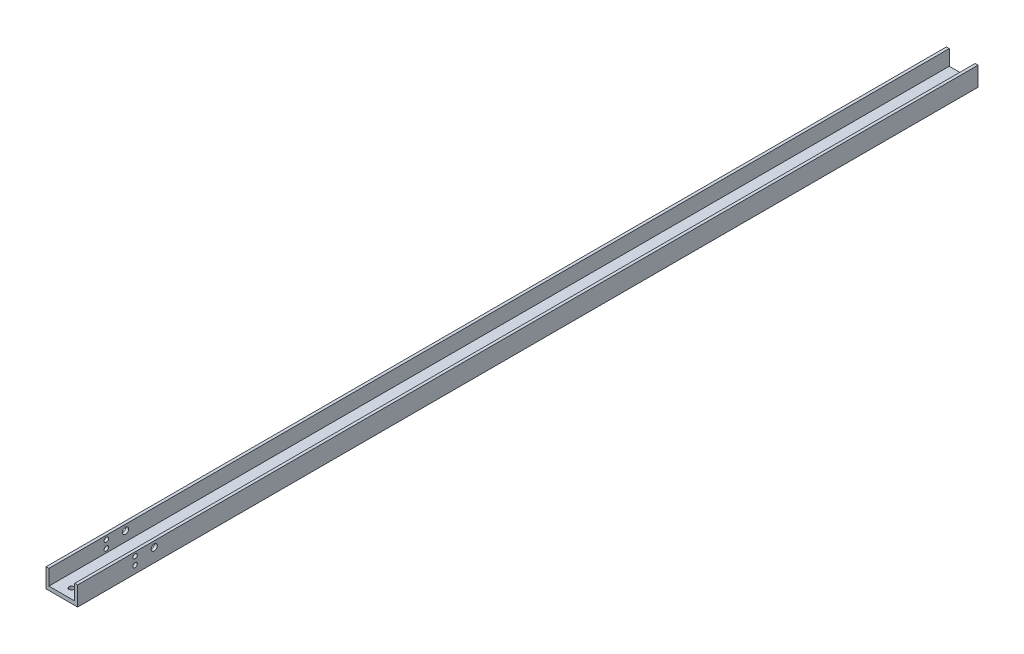
SolidWorks part; units mm, degrees
material "Alliage 1060"
ref_plane "Plan de face" through (0, 0, 0) normal (0, 0, 1) x (1, 0, 0)
ref_plane "Plan de dessus" through (0, 0, 0) normal (0, 1, 0) x (1, 0, 0)
ref_plane "Plan de droite" through (0, 0, 0) normal (1, 0, 0) x (0, 0, -1)
sketch "Esquisse1" plane through (0, 0, 0) normal (0, 0, 1) x (1, 0, 0)
  line L0 (-8.25, 0) -> (8.25, 0)
  line L1 (8.25, 0) -> (8.25, 10)
  line L2 (8.25, 10) -> (6.75, 10)
  line L3 (6.75, 10) -> (6.75, 2)
  line L4 (6.75, 2) -> (-6.75, 2)
  line L5 (0, 6.472) -> (0, -3.1073) construction
  line L6 (-6.75, 10) -> (-6.75, 2)
  line L7 (-8.25, 10) -> (-6.75, 10)
  line L8 (-8.25, 0) -> (-8.25, 10)
  point P10 (0, 2)
  point P13 (0, 0)
  dimension "D1" = 16.5
  dimension "D2" = 10
  dimension "D3" = 1.5
  dimension "D4" = 2
extrude "Boss.-Extru.1" add sketch "Esquisse1" along normal blind 470
sketch "Esquisse2" plane through (8.25, 0, 0) normal (1, 0, 0) x (0, 0, -1)
  line L0 (-440, 4) -> (-440, 13.011) construction
  line L1 (-470, 0) -> (-470, 10) construction
  line L2 (-470, 10) -> (0, 10) construction
  line L3 (-470, 2) -> (0, 2) construction
  circle A0 centre (-440, 8) radius 1.15
  circle A1 centre (-440, 4) radius 1.15
  circle A2 centre (-430, 7) radius 1.6
  dimension "D1" = 2.3
  dimension "D2" = 2.3
  dimension "D3" = 30
  dimension "D6" = 3.2
  dimension "D4" = 2
  dimension "D5" = 4
  dimension "D7" = 40
  dimension "D8" = 5
extrude "Enlèv. mat.-Extru.1" cut sketch "Esquisse2" against normal through all
hole_wizard "Trou pour taraudage pour trou taraudé M31" positions "Esquisse3" profile "Esquisse4" hole size "M3" standard "ISO" end condition through all
sketch "Esquisse3" plane through (0, 2, 0) normal (0, 1, 0) x (1, 0, 0)
  line L0 (6.75, -470) -> (-6.75, -470) construction
  line L2 (0, -545.3962) -> (0, -539.2293) construction
  point P2 (0, -465)
  dimension "D2" = 5
sketch "Esquisse4" plane through (0, 2, 465) normal (1, 0, 0) x (0, 0, 1)
  line L0 (0, 0) -> (0, 2)
  line L1 (0, 2) -> (1.25, 2)
  line L2 (1.25, 2) -> (1.25, 0)
  line L5 (1.25, 0) -> (0, 0)
  line L11 (0, -6.35) -> (0, 107.95) construction
  dimension "Diamètre du perçage jusqu'au prochain" = 2.5
  dimension "Profondeur du perçage jusqu'au prochain" = 2
sketch "Esquisse5" plane through (0, 2, 0) normal (0, 1, 0) x (1, 0, 0)
  line L0 (0, -467.2445) -> (0, -475.452) construction
  line L1 (6.75, -470) -> (6.75, 0) construction
  line L2 (-6.75, -470) -> (-6.75, 0) construction
  circle A0 centre (0, -467.2445) radius 1.25
  dimension "D1" = 2.5
extrude "Enlèv. mat.-Extru.2" [suppressed] cut sketch "Esquisse5" against normal through all
